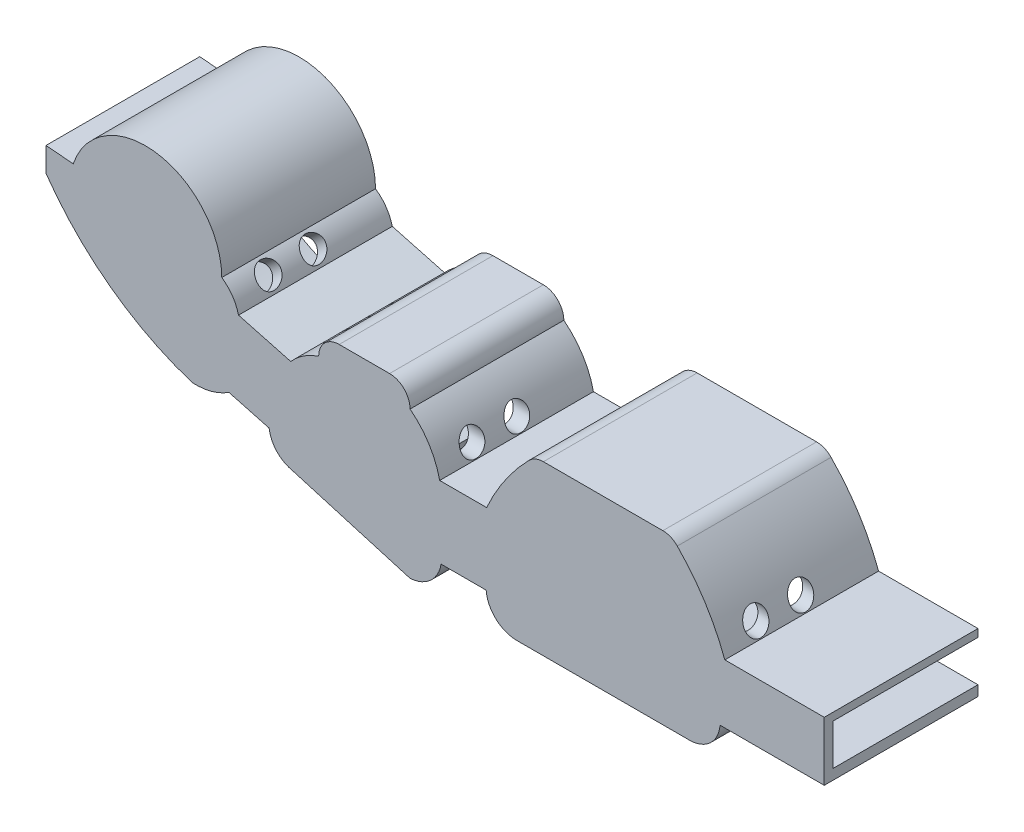
SolidWorks part; units mm, degrees
ref_plane "Front Plane" through (0, 0, 0) normal (0, 0, 1) x (1, 0, 0)
ref_plane "Top Plane" through (0, 0, 0) normal (0, 1, 0) x (1, 0, 0)
ref_plane "Right Plane" through (0, 0, 0) normal (1, 0, 0) x (0, 0, -1)
sketch "Sketch1" plane through (0, 0, 0) normal (0, 0, 1) x (1, 0, 0)
  line L23 (-11.1807, 10.652) -> (-11.4807, 9.152)
  line L24 (-11.4807, 9.152) -> (-11.7807, 10.652)
  line L25 (-11.7807, 10.652) -> (-12.4807, 10.652)
  line L36 (-12.4807, 10.652) -> (-12.7807, 9.152)
  line L40 (-12.7807, 9.152) -> (-13.0807, 10.652)
  line L41 (-13.0807, 10.652) -> (-13.7547, 10.652)
  line L47 (-13.7547, 10.652) -> (-14.0547, 9.152)
  line L48 (-14.0547, 9.152) -> (-14.3547, 10.652)
  line L49 (-14.3547, 10.652) -> (-15.0547, 10.652)
  line L50 (-15.0547, 10.652) -> (-15.3547, 9.152)
  line L51 (-15.3547, 9.152) -> (-15.6547, 10.652)
  line L52 (-15.6547, 10.652) -> (-16.3547, 10.652)
  line L53 (-16.3547, 10.652) -> (-16.6547, 9.152)
  line L54 (-16.6547, 9.152) -> (-16.9547, 10.652)
  line L55 (-16.9547, 10.652) -> (-17.6547, 10.652)
  line L80 (-17.6547, 10.652) -> (-17.9547, 9.152)
  line L167 (-44.1336, 10.6822) -> (-44.4336, 9.1822)
  line L170 (-46.0336, 10.6822) -> (-46.7336, 10.6822)
  line L171 (8.2817, 1.895) -> (-3.6348, 1.895)
  line L172 (-10.5067, 10.652) -> (-11.1807, 10.652)
  line L173 (-9.9067, 10.652) -> (-9.3532, 10.652)
  line L175 (-69.5436, 18.4578) -> (-69.8436, 19.5977)
  line L176 (-9.9067, 10.652) -> (-10.2067, 9.152)
  line L177 (-10.2067, 9.152) -> (-10.5067, 10.652)
  line L178 (-73.1421, 18.9938) -> (-73.4421, 17.6938)
  line L179 (-3.7183, -2.905) -> (8.2817, -2.905)
  line L180 (-2.7142, -4.105) -> (9.4817, -4.105)
  line L181 (-35.5381, 4.295) -> (-30.0408, 4.295)
  line L183 (9.4817, 2.795) -> (9.4817, -4.105)
  line L184 (8.2817, 1.895) -> (8.2817, -2.905)
  line L185 (-2.1578, 2.795) -> (9.4817, 2.795)
  line L186 (-77.5867, 9.2655) -> (-80.8842, 13.2092)
  line L187 (-45.4336, 10.6822) -> (-45.7336, 9.1822)
  line L188 (-66.9436, 17.8313) -> (-67.2436, 19.0854)
  line L189 (-57.9127, 0.2682) -> (-55.5052, -0.3779)
  line L190 (-81.6257, 12.3858) -> (-81.6257, 15.2174)
  line L192 (-42.8596, 10.6822) -> (-43.1596, 9.1822)
  line L193 (-43.1596, 9.1822) -> (-43.4596, 10.6822)
  line L194 (-44.7336, 10.6822) -> (-45.4336, 10.6822)
  line L195 (-80.8842, 13.2092) -> (-80.8842, 13.9453)
  line L196 (-44.4336, 9.1822) -> (-44.7336, 10.6822)
  line L197 (-64.3436, 15.6755) -> (-64.6436, 17.4876)
  line L198 (-70.5448, 19.5875) -> (-70.8448, 18.3969)
  line L199 (-60.3187, 8.3687) -> (-52.5921, 6.2951)
  line L200 (-23.1547, 9.152) -> (-23.4579, 10.6577)
  line L202 (-70.8448, 18.3969) -> (-71.1448, 19.5298)
  line L203 (-42.7174, 10.6822) -> (-42.8596, 10.6822)
  line L204 (-74.7402, 16.8139) -> (-75.0402, 17.886)
  line L205 (-78.8408, 12.3858) -> (-80.4985, 13.5047)
  line L206 (-73.4421, 17.6938) -> (-73.7421, 18.7169)
  line L207 (-47.0336, 9.1822) -> (-47.3336, 10.6822)
  line L208 (-64.0436, 16.8755) -> (-64.3436, 15.6755)
  line L209 (-80.8842, 13.9453) -> (-80.4985, 13.5047)
  line L210 (-65.6436, 16.9603) -> (-65.9436, 18.4574)
  line L211 (-67.9436, 19.313) -> (-68.2436, 18.263)
  line L212 (-37.0928, 3.095) -> (-29.0928, 3.095)
  line L213 (-62.7436, 14.8576) -> (-63.0436, 12.8576)
  line L214 (-68.2436, 18.263) -> (-68.5436, 19.4536)
  line L215 (-75.7418, 17.2662) -> (-76.0418, 15.3662)
  line L218 (-69.2436, 19.5578) -> (-69.5436, 18.4578)
  line L219 (-74.4402, 18.3139) -> (-74.7402, 16.8139)
  line L220 (-61.4607, 2.4628) -> (-53.62, 0.3587)
  line L222 (-63.0436, 12.8576) -> (-63.3436, 15.955)
  line L223 (-65.3436, 18.0603) -> (-65.6436, 16.9603)
  line L224 (-76.0418, 15.3662) -> (-76.3418, 16.5999)
  line L225 (-35.3722, -4.105) -> (-30.1012, -4.105)
  line L226 (-81.6257, 15.2174) -> (-78.4372, 14.9459)
  line L227 (-29.0971, -2.905) -> (-37.1235, -2.905)
  line L228 (-45.7336, 9.1822) -> (-46.0336, 10.6822)
  line L229 (-66.6436, 18.8313) -> (-66.9436, 17.8313)
  line L230 (-71.8426, 19.4048) -> (-72.1426, 18.1477)
  line L231 (-43.4596, 10.6822) -> (-44.1336, 10.6822)
  line L232 (-52.9727, 7.6397) -> (-59.0852, 9.2801)
  line L233 (-47.4174, 10.6822) -> (-47.3336, 10.6822)
  line L235 (-46.7336, 10.6822) -> (-47.0336, 9.1822)
  line L236 (-72.1426, 18.1477) -> (-72.4426, 19.2451)
  line L237 (-57.9127, 0.2682) -> (-60.21, 0.8847)
  line L238 (-19.2547, 9.152) -> (-19.5547, 10.652)
  line L239 (-17.9547, 9.152) -> (-18.2547, 10.652)
  line L240 (-20.2547, 10.652) -> (-20.5547, 9.152)
  line L241 (-18.2547, 10.652) -> (-18.9547, 10.652)
  line L242 (-18.9547, 10.652) -> (-19.2547, 9.152)
  line L243 (-20.8547, 10.652) -> (-21.5547, 10.652)
  line L244 (-20.5547, 9.152) -> (-20.8547, 10.652)
  line L245 (-19.5547, 10.652) -> (-20.2547, 10.652)
  line L246 (-21.5547, 10.652) -> (-21.8547, 9.152)
  line L247 (-22.1547, 10.652) -> (-22.8547, 10.652)
  line L248 (-22.8547, 10.652) -> (-23.1547, 9.152)
  line L249 (-21.8547, 9.152) -> (-22.1547, 10.652)
  line L253 (-23.3968, 12.2681) -> (-9.4143, 12.2681)
  line L254 (-26.0691, -6.2141) -> (-6.7463, -6.2141)
  line L255 (-6.3025, -7.4141) -> (-26.513, -7.4141)
  line L256 (-47.304, 12.2025) -> (-41.404, 12.2025)
  line L257 (-51.326, -2.5288) -> (-40.0703, -5.8983)
  line L258 (-39.0122, -7.3625) -> (-52.779, -3.3191)
  arc A66 (-2.7142, -4.105) -> (-6.3025, -7.4141) centre (-6.3025, -3.8141) cw
  arc A67 (-3.7183, -2.905) -> (-6.7463, -6.2141) centre (-6.7023, -3.2144) cw
  arc A69 (-7.343, 8.6822) -> (-9.3532, 10.652) centre (-10.3911, 7.5822) ccw
  arc A70 (-7.343, 8.6822) -> (-3.6348, 1.895) centre (-11.6135, 1.9424) cw
  arc A71 (-2.1578, 2.795) -> (-7.7202, 11.551) centre (-25.381, -5.8132) ccw
  arc A72 (-9.4143, 12.2681) -> (-7.7202, 11.551) centre (-9.4143, 9.9085) cw
  arc A73 (-62.0436, 11.2299) -> (-62.7436, 14.8576) centre (-70.0767, 11.5612) ccw
  arc A74 (-49.4174, 8.6822) -> (-52.5921, 6.2951) centre (-47.5158, 2.8486) ccw
  arc A75 (-23.3968, 12.2681) -> (-25.0909, 11.551) centre (-23.3968, 9.9085) ccw
  arc A76 (-75.0402, 17.886) -> (-75.7418, 17.2662) centre (-70.0767, 11.5612) ccw
  arc A77 (-29.0971, -2.905) -> (-26.0691, -6.2141) centre (-26.1131, -3.2144) ccw
  arc A78 (-81.6257, 12.3858) -> (-64.5211, -0.2669) centre (-54.2173, 31.5502) ccw
  arc A79 (-65.9436, 18.4574) -> (-66.6436, 18.8313) centre (-70.0767, 11.5612) ccw
  arc A80 (-69.8436, 19.5977) -> (-70.5448, 19.5875) centre (-70.0767, 11.5612) ccw
  arc A81 (-71.1448, 19.5298) -> (-71.8426, 19.4048) centre (-70.0767, 11.5612) ccw
  arc A82 (-47.304, 12.2025) -> (-49.704, 9.8025) centre (-47.304, 9.8025) ccw
  arc A83 (-40.0703, -5.8983) -> (-37.1235, -2.905) centre (-40.3823, -2.644) ccw
  arc A84 (-77.5867, 9.2655) -> (-64.963, 0.8179) centre (-56.8402, 26.6123) ccw
  arc A85 (-40.7174, 8.6822) -> (-42.7174, 10.6822) centre (-42.7174, 8.6822) ccw
  arc A86 (-47.4174, 10.6822) -> (-49.4174, 8.6822) centre (-47.4174, 8.6822) ccw
  arc A87 (-30.1012, -4.105) -> (-26.513, -7.4141) centre (-26.513, -3.8141) ccw
  arc A88 (-35.5381, 4.295) -> (-39.004, 9.8025) centre (-44.8924, 2.2526) ccw
  arc A89 (-67.2436, 19.0854) -> (-67.9436, 19.313) centre (-70.0767, 11.5612) ccw
  arc A90 (-72.4426, 19.2451) -> (-73.1421, 18.9938) centre (-70.0767, 11.5612) ccw
  arc A91 (-78.4372, 14.9459) -> (-61.0466, 12.1147) centre (-69.9779, 12.081) cw
  arc A92 (-63.3436, 15.955) -> (-64.0436, 16.8755) centre (-70.0767, 11.5612) ccw
  arc A93 (-64.963, 0.8179) -> (-61.4607, 2.4628) centre (-64.1865, 3.7157) ccw
  arc A94 (-73.7421, 18.7169) -> (-74.4402, 18.3139) centre (-70.0767, 11.5612) ccw
  arc A95 (-49.704, 9.8025) -> (-52.9727, 7.6397) centre (-47.422, 2.8022) ccw
  arc A96 (-24.9838, 9.9746) -> (-25.4681, 8.6822) centre (-23.5017, 8.6822) ccw
  arc A97 (-39.0122, -7.3625) -> (-35.3722, -4.105) centre (-39.2396, -3.446) ccw
  arc A98 (-76.3418, 16.5999) -> (-78.0314, 12.7286) centre (-70.0767, 11.5612) ccw
  arc A99 (-53.62, 0.3587) -> (-51.326, -2.5288) centre (-50.7468, 0.2864) ccw
  arc A100 (-60.3187, 8.3687) -> (-62.0436, 11.2299) centre (-64.3325, 7.8995) ccw
  arc A101 (-23.4579, 10.6577) -> (-24.9838, 9.9746) centre (-23.4814, 8.6645) ccw
  arc A102 (-68.5436, 19.4536) -> (-69.2436, 19.5578) centre (-70.0767, 11.5612) ccw
  arc A103 (-39.004, 9.8025) -> (-41.404, 12.2025) centre (-41.404, 9.8025) ccw
  arc A104 (-30.0408, 4.295) -> (-25.0909, 11.551) centre (-7.4301, -5.8132) cw
  arc A105 (-55.5052, -0.3779) -> (-52.779, -3.3191) centre (-52.084, 0.0591) ccw
  arc A106 (-64.6436, 17.4876) -> (-65.3436, 18.0603) centre (-70.0767, 11.5612) ccw
  arc A107 (-60.21, 0.8847) -> (-64.5211, -0.2669) centre (-64.1411, 6.9561) cw
  arc A108 (-37.0928, 3.095) -> (-40.7174, 8.6822) centre (-44.988, 1.9424) ccw
  arc A109 (-59.0852, 9.2801) -> (-61.0466, 12.1147) centre (-63.7933, 8.1183) ccw
  arc A110 (-25.4681, 8.6822) -> (-29.0928, 3.095) centre (-21.1976, 1.9424) ccw
  arc A111 (-78.0314, 12.7286) -> (-78.8408, 12.3858) centre (-71.5152, -3.7856) ccw
  dimension "D14" = 12
  dimension "D18" = 4.8
  dimension "D19" = 6.9
  dimension "D20" = 11.9164
extrude "Walls" add sketch "Sketch1" along normal blind 16 contours L242 region at (-36.8277, 4.9059, 0)
sketch "Sketch2" plane through (0, 0, 0) normal (0, 0, -1) x (-1, 0, 0)
  line L10 (59.0852, 9.2801) -> (52.9727, 7.6397)
  line L12 (59.0852, 9.2801) -> (52.9727, 7.6397)
  line L14 (47.304, 12.2025) -> (41.404, 12.2025)
  line L15 (2.1578, 2.795) -> (-9.4817, 2.795)
  line L16 (47.304, 12.2025) -> (41.404, 12.2025)
  line L17 (2.1578, 2.795) -> (-9.4817, 2.795)
  line L18 (-9.4817, 2.795) -> (-9.4817, -4.105)
  line L19 (35.5381, 4.295) -> (30.0408, 4.295)
  line L22 (35.5381, 4.295) -> (30.0408, 4.295)
  line L37 (-9.4817, 2.795) -> (-9.4817, -4.105)
  line L38 (-9.4817, -4.105) -> (2.7142, -4.105)
  line L39 (-9.4817, -4.105) -> (2.7142, -4.105)
  line L40 (23.3968, 12.2681) -> (9.4143, 12.2681)
  line L42 (23.3968, 12.2681) -> (9.4143, 12.2681)
  line L44 (6.3025, -7.4141) -> (26.513, -7.4141)
  line L47 (6.3025, -7.4141) -> (26.513, -7.4141)
  line L49 (30.1012, -4.105) -> (35.3722, -4.105)
  line L50 (30.1012, -4.105) -> (35.3722, -4.105)
  line L51 (39.0122, -7.3625) -> (52.779, -3.3191)
  line L52 (39.0122, -7.3625) -> (52.779, -3.3191)
  line L53 (55.5052, -0.3779) -> (60.21, 0.8847)
  line L54 (55.5052, -0.3779) -> (60.21, 0.8847)
  line L55 (81.6257, 12.3858) -> (81.6257, 15.2174)
  line L56 (81.6257, 12.3858) -> (81.6257, 15.2174)
  line L57 (81.6257, 15.2174) -> (78.4372, 14.9459)
  line L58 (81.6257, 15.2174) -> (78.4372, 14.9459)
  arc A16 (9.4143, 12.2681) -> (7.7202, 11.551) centre (9.4143, 9.9085) ccw
  arc A17 (9.4143, 12.2681) -> (7.7202, 11.551) centre (9.4143, 9.9085) ccw
  arc A18 (52.9727, 7.6397) -> (49.704, 9.8025) centre (47.422, 2.8022) ccw
  arc A19 (52.9727, 7.6397) -> (49.704, 9.8025) centre (47.422, 2.8022) ccw
  arc A20 (49.704, 9.8025) -> (47.304, 12.2025) centre (47.304, 9.8025) ccw
  arc A21 (49.704, 9.8025) -> (47.304, 12.2025) centre (47.304, 9.8025) ccw
  arc A22 (41.404, 12.2025) -> (39.004, 9.8025) centre (41.404, 9.8025) ccw
  arc A23 (41.404, 12.2025) -> (39.004, 9.8025) centre (41.404, 9.8025) ccw
  arc A24 (39.004, 9.8025) -> (35.5381, 4.295) centre (44.8924, 2.2526) ccw
  arc A25 (7.7202, 11.551) -> (2.1578, 2.795) centre (25.381, -5.8132) ccw
  arc A26 (7.7202, 11.551) -> (2.1578, 2.795) centre (25.381, -5.8132) ccw
  arc A27 (2.7142, -4.105) -> (6.3025, -7.4141) centre (6.3025, -3.8141) ccw
  arc A28 (2.7142, -4.105) -> (6.3025, -7.4141) centre (6.3025, -3.8141) ccw
  arc A29 (39.004, 9.8025) -> (35.5381, 4.295) centre (44.8924, 2.2526) ccw
  arc A30 (30.0408, 4.295) -> (25.0909, 11.551) centre (7.4301, -5.8132) ccw
  arc A31 (30.0408, 4.295) -> (25.0909, 11.551) centre (7.4301, -5.8132) ccw
  arc A32 (25.0909, 11.551) -> (23.3968, 12.2681) centre (23.3968, 9.9085) ccw
  arc A33 (25.0909, 11.551) -> (23.3968, 12.2681) centre (23.3968, 9.9085) ccw
  arc A34 (26.513, -7.4141) -> (30.1012, -4.105) centre (26.513, -3.8141) ccw
  arc A35 (26.513, -7.4141) -> (30.1012, -4.105) centre (26.513, -3.8141) ccw
  arc A54 (35.3722, -4.105) -> (39.0122, -7.3625) centre (39.2396, -3.446) ccw
  arc A55 (35.3722, -4.105) -> (39.0122, -7.3625) centre (39.2396, -3.446) ccw
  arc A56 (52.779, -3.3191) -> (55.5052, -0.3779) centre (52.084, 0.0591) ccw
  arc A57 (52.779, -3.3191) -> (55.5052, -0.3779) centre (52.084, 0.0591) ccw
  arc A58 (60.21, 0.8847) -> (64.5211, -0.2669) centre (64.1411, 6.9561) ccw
  arc A59 (60.21, 0.8847) -> (64.5211, -0.2669) centre (64.1411, 6.9561) ccw
  arc A60 (64.5211, -0.2669) -> (81.6257, 12.3858) centre (54.2173, 31.5502) ccw
  arc A61 (64.5211, -0.2669) -> (81.6257, 12.3858) centre (54.2173, 31.5502) ccw
  arc A62 (78.4372, 14.9459) -> (61.0466, 12.1147) centre (69.9779, 12.081) ccw
  arc A63 (78.4372, 14.9459) -> (61.0466, 12.1147) centre (69.9779, 12.081) ccw
  arc A64 (61.0466, 12.1147) -> (59.0852, 9.2801) centre (63.7933, 8.1183) ccw
  arc A65 (61.0466, 12.1147) -> (59.0852, 9.2801) centre (63.7933, 8.1183) ccw
  dimension "D1" = 0
extrude "Base" add sketch "Sketch2" along normal blind 1
sketch "Sketch3" [suppressed] plane through (0, 0, 0) normal (0, 0, 1) x (1, 0, 0)
  line L4 (-65.1711, 5.3832) -> (-63.3958, 4.9067) construction
  line L5 (-84.8697, 19.5134) -> (-85.1843, 17.3997) construction
  line L6 (-51.77, 3.095) -> (-68.5693, 3.095) construction
  line L7 (-68.5693, 6.2951) -> (-68.5693, 3.095) construction
  line L8 (-51.77, 3.095) -> (-54.6697, 3.095) construction
  line L9 (-68.5693, 6.2951) -> (-65.1711, 5.3832) construction
  line L10 (-56.4697, 3.095) -> (-54.6697, 3.095) construction
  line L11 (-80.595, 9.5224) -> (-82.2789, 9.9743)
  line L12 (-80.595, 9.5224) -> (-76.2959, 8.3687) construction
  line L13 (-91.8537, 12.2226) -> (-90.116, 11.8146)
  line L14 (-82.2789, 9.9743) -> (-90.116, 11.8146) construction
  line L15 (-40.77, 3.095) -> (-37.27, 3.095) construction
  line L16 (-3.6422, 1.595) -> (-7.1422, 1.595) construction
  line L17 (-40.77, 3.095) -> (-3.7183, 3.095) construction
  line L18 (-22.2442, 8.652) -> (-22.2442, 3.095) construction
  line L19 (-22.8547, 10.652) -> (-22.1547, 10.652) construction
  line L20 (-22.2442, 10.652) -> (-22.2442, 8.652) construction
  line L21 (-37.27, 3.095) -> (-34.1769, 3.095) construction
  line L22 (-11.7175, 3.095) -> (-7.1422, 1.595) construction
  arc A1 (-82.2789, 9.9743) -> (-90.116, 11.8146) centre (-86.0365, 11.58) ccw
  arc A2 (-91.8537, 12.2226) -> (-80.595, 9.5224) centre (-86.0443, 11.6231) cw
  arc A3 (-54.6697, 3.095) -> (-65.1711, 5.3832) centre (-60.1697, 3.095) ccw construction
  arc A4 (-84.5208, 19.4536) -> (-85.2208, 19.5578) centre (-86.0539, 11.5612) ccw construction
  arc A5 (-56.4697, 3.095) -> (-63.3958, 4.9067) centre (-60.1697, 3.095) ccw construction
  arc A6 (-3.6422, 1.595) -> (-7.343, 8.6822) centre (-11.6135, 1.9424) ccw construction
  arc A7 (-7.1422, 1.595) -> (-37.27, 3.095) centre (-22.9472, -12.5401) ccw construction
  arc A8 (-11.7175, 3.095) -> (-34.1769, 3.095) centre (-22.9472, -12.5401) ccw construction
  dimension "D1" = 11
  dimension "D2" = 2.137
  dimension "D3" = 7.4
  dimension "D8" = 38.5
  dimension "D4" = 3.5184
  dimension "D5" = 3.5
  dimension "D6" = 3.5
  dimension "D7" = 2
sketch "Sketch4" [suppressed] plane through (0, 0, 16) normal (0, 0, 1) x (1, 0, 0)
  line L7 (-69.5947, 0.3005) -> (-71.4824, -0.3779)
  line L10 (-71.4824, -0.3779) -> (-76.1872, 0.8847)
  line L11 (-76.1872, 0.8847) -> (-77.6773, 2.0433)
  line L12 (-40.77, 3.095) -> (-41.1043, 4.1128)
  line L13 (-41.1043, 4.1128) -> (-49.5364, 4.1128)
  line L16 (-67.7226, 6.3478) -> (-68.9499, 7.6397)
  line L17 (-68.9499, 7.6397) -> (-75.0624, 9.2801)
  line L18 (-75.0624, 9.2801) -> (-76.3177, 7.7352)
  line L19 (-49.5364, 4.1128) -> (-51.77, 3.095)
  line L20 (-40.7743, -2.905) -> (-41.0926, -4.1129)
  line L21 (-41.0926, -4.1129) -> (-49.3636, -4.1129)
  line L22 (-49.3636, -4.1129) -> (-51.8007, -2.905)
  arc A0 (-67.7226, 6.3478) -> (-76.3177, 7.7352) centre (-69.7742, 20.955) cw
  arc A1 (-69.5947, 0.3005) -> (-77.6773, 2.0433) centre (-76.3689, -11.5028) ccw
  arc A2 (-40.7743, -2.905) -> (-51.8007, -2.905) centre (-46.2875, -28.5004) ccw
  arc A3 (-40.77, 3.095) -> (-51.77, 3.095) centre (-46.27, 28.5687) cw
extrude "Joint Width" [suppressed] add sketch "Sketch4" against normal blind 16
ref_plane "SideAnchorPlane" through (0, 0, 2.5) normal (0, 0, 1) x (1, 0, 0)
ref_plane "CentralAnchorPlane" through (0, 0, 13) normal (0, 0, 1) x (1, 0, 0)
sketch "Sketch5" [suppressed] plane through (0, 0, 3) normal (0, 0, 1) x (1, 0, 0)
  line L0 (-76.2959, 8.3687) -> (-68.5693, 6.2951) construction
  line L1 (-76.592, 9.4835) -> (-67.8744, 7.144) construction
  line L2 (-77.4258, 10.7304) -> (-66.9487, 7.9187) construction
  line L3 (-76.592, 9.4835) -> (-88.7757, 4.7797)
  line L4 (-77.4258, 10.7304) -> (-90.1205, 5.8293)
  line L5 (-78.0158, 11.7317) -> (-91.096, 6.6818)
  line L6 (-76.2959, 8.3687) -> (-87.6359, 3.9906)
  line L7 (-78.0158, 11.7317) -> (-77.4258, 10.7304)
  line L9 (-76.592, 9.4835) -> (-76.0479, 8.9395)
  line L10 (-76.0479, 8.9395) -> (-76.2959, 8.3687)
  line L11 (-91.096, 6.6818) -> (-91.096, 6.0024)
  line L12 (-91.096, 6.0024) -> (-90.1205, 5.8293)
  line L13 (-88.7757, 4.7797) -> (-88.5883, 3.9906)
  line L14 (-88.5883, 3.9906) -> (-87.6359, 3.9906)
  arc A0 (-76.2959, 8.3687) -> (-78.0208, 11.2299) centre (-80.3097, 7.8995) ccw construction
  arc A1 (-65.3947, 8.6822) -> (-68.5693, 6.2951) centre (-63.493, 2.8486) ccw construction
  arc A2 (-76.2959, 8.3687) -> (-78.0208, 11.2299) centre (-80.3097, 7.8995) ccw construction
  arc A4 (-93.5639, 9.2655) -> (-80.9402, 0.8179) centre (-72.8174, 26.6123) ccw construction
  arc A5 (-93.5639, 9.2655) -> (-80.9402, 0.8179) centre (-72.8174, 26.6123) ccw construction
  dimension "D1" = 1
  dimension "D2" = 1.5
  dimension "D3" = 1.1466
  dimension "D4" = 1.1466
extrude "Boss-Extrude2" [suppressed] add sketch "Sketch5" along normal blind 1 and the other way blind 1 separate body
sketch "Sketch6" [suppressed] plane through (0, 0, 4) normal (0, 0, 1) x (1, 0, 0)
  line L1 (-87.6359, 3.9906) -> (-76.2959, 8.3687)
  line L4 (-78.0158, 11.7317) -> (-91.096, 6.6818)
  line L5 (-91.096, 6.6818) -> (-91.7792, 6.284)
  line L6 (-91.7792, 6.284) -> (-88.4163, 3.7031)
  line L7 (-88.4163, 3.7031) -> (-87.6359, 3.9906)
  line L8 (-78.0158, 11.7317) -> (-75.9969, 10.8669)
  line L9 (-75.9969, 10.8669) -> (-76.2959, 8.3687)
  arc A0 (-93.5639, 9.2655) -> (-80.9402, 0.8179) centre (-72.8174, 26.6123) ccw construction
extrude "Boss-Extrude4" [suppressed] add sketch "Sketch6" along normal blind 1
sketch "Sketch7" [suppressed] plane through (0, 0, 2) normal (0, 0, -1) x (-1, 0, 0)
  line L0 (87.6359, 3.9906) -> (90.1015, 4.9746)
  line L1 (90.1015, 4.9746) -> (91.096, 6.6818)
  line L2 (91.096, 6.6818) -> (78.0158, 11.7317)
  line L3 (78.0158, 11.7317) -> (76.2959, 10.4542)
  line L4 (76.2959, 10.4542) -> (76.2959, 8.3687)
  line L5 (76.2959, 8.3687) -> (87.6359, 3.9906)
extrude "Boss-Extrude5" [suppressed] add sketch "Sketch7" along normal blind 1
extrude "Boss-Extrude6" [suppressed] add sketch "Sketch3" along normal up to surface (16 mm away)
ref_plane "Plane3" through (-55, 0, 0) normal (1, 0, 0) x (0, 0, -1)
sketch "Sketch14" plane through (-55, 0, 0) normal (1, 0, 0) x (0, 0, -1)
  line L0 (-16, 3.095) -> (1, 3.095) construction
  line L1 (1, 2.795) -> (1, 11.551) construction
  line L2 (-16, 8.4472) -> (1, 8.4472) construction
  line L3 (-16, 11.551) -> (-16, 2.795) construction
  line L4 (-7.5, 8.4472) -> (-7.5, 3.095) construction
  line L6 (-7.5, 5.7711) -> (-16, 5.7711) construction
  line L7 (-16, 2.795) -> (-16, 3.095) construction
  line L8 (-16, 8.4472) -> (-16, 3.095) construction
  circle A4 centre (-12.75, 5.7711) radius 1.4
  circle A5 centre (-2.25, 5.7711) radius 1.4 construction
  circle A6 centre (-7.5, 5.7711) radius 1.4
  dimension "D1" = 2.8
  dimension "D2" = 5.25
  dimension "D3" = 0.3
extrude "Cut-Extrude2" cut sketch "Sketch14" along normal up to surface (26.8022 mm away) up to face at (-27.5858, 6.0868, 8)
sketch "Sketch15" plane through (0, 0, 0) normal (1, 0, 0) x (0, 0, -1)
  line L1 (-16, 2.795) -> (1, 2.795) construction
  line L5 (1, 2.795) -> (1, 5.795) construction
  line L6 (1, 2.795) -> (1, 11.551) construction
  line L7 (1, 5.795) -> (-16, 5.795) construction
  line L8 (-7.5, 5.795) -> (-7.5, 2.795) construction
  line L9 (-16, 11.551) -> (-16, 2.795) construction
  line L10 (-7.5, 4.295) -> (-16, 4.295) construction
  circle A4 centre (-12.75, 4.295) radius 1.4
  circle A5 centre (-2.25, 4.295) radius 1.4 construction
  circle A6 centre (-7.5, 4.295) radius 1.4
  dimension "D2" = 5.25
  dimension "D1" = 2.8
extrude "Cut-Extrude3" cut sketch "Sketch15" against normal up to surface (3.9894 mm away) up to face at (-5.0502, 5.5283, 8)
ref_plane "Plane4" through (-30.1263, -25.259, 0) normal (0.7663, 0.6425, 0) x (0, 0, -1)
sketch "Sketch16" plane through (-30.1263, -25.259, 0) normal (0.7663, 0.6425, 0) x (0, 0, -1)
  line L1 (-2.2201, 49.6951) -> (-13, 49.6951) construction
  line L2 (-13, 55) -> (-13, -55) construction
  line L3 (-16, 48.5053) -> (-16, 45.0729) construction
  line L6 (-16, 46.7891) -> (1, 46.7891) construction
  line L7 (-7.61, 49.6951) -> (-13, 49.6951) construction
  line L12 (-16, 48.5053) -> (1, 48.5053) construction
  line L13 (-7.5, 48.5053) -> (-7.5, 45.0729) construction
  circle A0 centre (-2.2201, 49.6951) radius 1.4 construction
  circle A1 centre (-12.86, 49.6951) radius 1.4 construction
  circle A2 centre (-12.75, 46.7891) radius 1.4
  circle A3 centre (-2.25, 46.7891) radius 1.4 construction
  circle A4 centre (-7.5, 46.7891) radius 1.4
  dimension "D1" = 2.8
  dimension "D4" = 5.25
  dimension "D5" = 2.8
  dimension "D3" = 5.25
extrude "Cut-Extrude4" cut sketch "Sketch16" against normal up to surface and the other way up to surface up to face at (-73.5899, 5.3613, 7.5) other way up to face at (-59.9357, 10.7875, 7.5)
ref_plane "Plane5" through (-49.2204, 17.9364, 0) normal (-0.9396, 0.3424, 0) x (0, 0, -1)
sketch "Sketch18" plane through (-49.2204, 17.9364, 0) normal (-0.9396, 0.3424, 0) x (0, 0, -1)
  line L0 (-16, 8.7623) -> (0, 8.7623) construction
  line L1 (-16, 7.8123) -> (-16, 9.3835) construction
  line L2 (-16, 10.9591) -> (-16, 7.8079) construction
  line L3 (-16, 9.3835) -> (1, 9.3835) construction
  line L4 (1, 7.8079) -> (1, 10.9591) construction
  line L5 (-16, 7.8123) -> (1, 7.8123) construction
  line L6 (-7.5, 9.3835) -> (-7.5, 7.8123) construction
  line L14 (-7.5, 9.3835) -> (-16, 9.3835) construction
  circle A2 centre (-12.75, 9.3835) radius 1.4
  circle A3 centre (-2.25, 9.3835) radius 1.4 construction
  circle A4 centre (-7.5, 9.3835) radius 1.4
  dimension "D1" = 2.8
  dimension "D3" = 17
  dimension "D4" = 0.95
extrude "Cut-Extrude5" cut sketch "Sketch18" against normal up to surface (1.3124 mm away) up to face at (-51.6727, 7.1718, 9.1219)
sketch "Sketch19" plane through (0, 0, 0) normal (0, 0, 1) x (1, 0, 0)
  line L477 (-11.1807, 10.652) -> (-11.4807, 9.152)
  line L490 (-11.4807, 9.152) -> (-11.7807, 10.652)
  line L542 (-11.7807, 10.652) -> (-12.4807, 10.652)
  line L685 (-12.4807, 10.652) -> (-12.7807, 9.152)
  line L686 (-12.7807, 9.152) -> (-13.0807, 10.652)
  line L687 (-13.0807, 10.652) -> (-13.7547, 10.652)
  line L688 (-13.7547, 10.652) -> (-14.0547, 9.152)
  line L689 (-14.0547, 9.152) -> (-14.3547, 10.652)
  line L690 (-14.3547, 10.652) -> (-15.0547, 10.652)
  line L691 (-15.0547, 10.652) -> (-15.3547, 9.152)
  line L692 (-15.3547, 9.152) -> (-15.6547, 10.652)
  line L693 (-15.6547, 10.652) -> (-16.3547, 10.652)
  line L694 (-16.3547, 10.652) -> (-16.6547, 9.152)
  line L695 (-16.6547, 9.152) -> (-16.9547, 10.652)
  line L696 (-16.9547, 10.652) -> (-17.6547, 10.652)
  line L697 (-17.6547, 10.652) -> (-17.9547, 9.152)
  line L698 (-44.1336, 10.6822) -> (-44.4336, 9.1822)
  line L699 (-46.0336, 10.6822) -> (-46.7336, 10.6822)
  line L700 (8.2817, 1.895) -> (-3.6348, 1.895)
  line L701 (-10.5067, 10.652) -> (-11.1807, 10.652)
  line L702 (-9.9067, 10.652) -> (-9.3532, 10.652)
  line L703 (-69.5436, 18.4578) -> (-69.8436, 19.5977)
  line L704 (-9.9067, 10.652) -> (-10.2067, 9.152)
  line L705 (-10.2067, 9.152) -> (-10.5067, 10.652)
  line L706 (-73.1421, 18.9938) -> (-73.4421, 17.6938)
  line L707 (-3.7183, -2.905) -> (8.2817, -2.905)
  line L711 (8.2817, 1.895) -> (8.2817, -2.905)
  line L713 (-77.5867, 9.2655) -> (-80.8842, 13.2092)
  line L714 (-45.4336, 10.6822) -> (-45.7336, 9.1822)
  line L715 (-66.9436, 17.8313) -> (-67.2436, 19.0854)
  line L718 (-42.8596, 10.6822) -> (-43.1596, 9.1822)
  line L719 (-43.1596, 9.1822) -> (-43.4596, 10.6822)
  line L720 (-44.7336, 10.6822) -> (-45.4336, 10.6822)
  line L721 (-80.8842, 13.2092) -> (-80.8842, 13.9453)
  line L722 (-44.4336, 9.1822) -> (-44.7336, 10.6822)
  line L723 (-64.3436, 15.6755) -> (-64.6436, 17.4876)
  line L724 (-70.5448, 19.5875) -> (-70.8448, 18.3969)
  line L725 (-60.3187, 8.3687) -> (-52.5921, 6.2951)
  line L726 (-23.1547, 9.152) -> (-23.4579, 10.6577)
  line L727 (-70.8448, 18.3969) -> (-71.1448, 19.5298)
  line L728 (-42.7174, 10.6822) -> (-42.8596, 10.6822)
  line L729 (-74.7402, 16.8139) -> (-75.0402, 17.886)
  line L730 (-78.8408, 12.3858) -> (-80.4985, 13.5047)
  line L731 (-73.4421, 17.6938) -> (-73.7421, 18.7169)
  line L732 (-47.0336, 9.1822) -> (-47.3336, 10.6822)
  line L733 (-64.0436, 16.8755) -> (-64.3436, 15.6755)
  line L734 (-80.8842, 13.9453) -> (-80.4985, 13.5047)
  line L735 (-65.6436, 16.9603) -> (-65.9436, 18.4574)
  line L736 (-67.9436, 19.313) -> (-68.2436, 18.263)
  line L737 (-37.0928, 3.095) -> (-29.0928, 3.095)
  line L738 (-62.7436, 14.8576) -> (-63.0436, 12.8576)
  line L739 (-68.2436, 18.263) -> (-68.5436, 19.4536)
  line L740 (-75.7418, 17.2662) -> (-76.0418, 15.3662)
  line L741 (-69.2436, 19.5578) -> (-69.5436, 18.4578)
  line L742 (-74.4402, 18.3139) -> (-74.7402, 16.8139)
  line L743 (-61.4607, 2.4628) -> (-53.62, 0.3587)
  line L744 (-63.0436, 12.8576) -> (-63.3436, 15.955)
  line L745 (-65.3436, 18.0603) -> (-65.6436, 16.9603)
  line L746 (-76.0418, 15.3662) -> (-76.3418, 16.5999)
  line L749 (-29.0971, -2.905) -> (-37.1235, -2.905)
  line L750 (-45.7336, 9.1822) -> (-46.0336, 10.6822)
  line L751 (-66.6436, 18.8313) -> (-66.9436, 17.8313)
  line L752 (-71.8426, 19.4048) -> (-72.1426, 18.1477)
  line L753 (-43.4596, 10.6822) -> (-44.1336, 10.6822)
  line L755 (-47.4174, 10.6822) -> (-47.3336, 10.6822)
  line L756 (-46.7336, 10.6822) -> (-47.0336, 9.1822)
  line L757 (-72.1426, 18.1477) -> (-72.4426, 19.2451)
  line L759 (-19.2547, 9.152) -> (-19.5547, 10.652)
  line L760 (-17.9547, 9.152) -> (-18.2547, 10.652)
  line L761 (-20.2547, 10.652) -> (-20.5547, 9.152)
  line L762 (-18.2547, 10.652) -> (-18.9547, 10.652)
  line L763 (-18.9547, 10.652) -> (-19.2547, 9.152)
  line L764 (-20.8547, 10.652) -> (-21.5547, 10.652)
  line L765 (-20.5547, 9.152) -> (-20.8547, 10.652)
  line L766 (-19.5547, 10.652) -> (-20.2547, 10.652)
  line L767 (-21.5547, 10.652) -> (-21.8547, 9.152)
  line L768 (-22.1547, 10.652) -> (-22.8547, 10.652)
  line L769 (-22.8547, 10.652) -> (-23.1547, 9.152)
  line L770 (-21.8547, 9.152) -> (-22.1547, 10.652)
  line L772 (-26.0691, -6.2141) -> (-6.7463, -6.2141)
  line L775 (-51.326, -2.5288) -> (-40.0703, -5.8983)
  arc A251 (-3.7183, -2.905) -> (-6.7463, -6.2141) centre (-6.7023, -3.2144) cw
  arc A252 (-7.343, 8.6822) -> (-9.3532, 10.652) centre (-10.3911, 7.5822) ccw
  arc A253 (-7.343, 8.6822) -> (-3.6348, 1.895) centre (-11.6135, 1.9424) cw
  arc A256 (-62.0436, 11.2299) -> (-62.7436, 14.8576) centre (-70.0767, 11.5612) ccw
  arc A257 (-49.4174, 8.6822) -> (-52.5921, 6.2951) centre (-47.5158, 2.8486) ccw
  arc A259 (-75.0402, 17.886) -> (-75.7418, 17.2662) centre (-70.0767, 11.5612) ccw
  arc A260 (-29.0971, -2.905) -> (-26.0691, -6.2141) centre (-26.1131, -3.2144) ccw
  arc A262 (-65.9436, 18.4574) -> (-66.6436, 18.8313) centre (-70.0767, 11.5612) ccw
  arc A263 (-69.8436, 19.5977) -> (-70.5448, 19.5875) centre (-70.0767, 11.5612) ccw
  arc A264 (-71.1448, 19.5298) -> (-71.8426, 19.4048) centre (-70.0767, 11.5612) ccw
  arc A266 (-40.0703, -5.8983) -> (-37.1235, -2.905) centre (-40.3823, -2.644) ccw
  arc A267 (-77.5867, 9.2655) -> (-64.963, 0.8179) centre (-56.8402, 26.6123) ccw
  arc A268 (-40.7174, 8.6822) -> (-42.7174, 10.6822) centre (-42.7174, 8.6822) ccw
  arc A269 (-47.4174, 10.6822) -> (-49.4174, 8.6822) centre (-47.4174, 8.6822) ccw
  arc A272 (-67.2436, 19.0854) -> (-67.9436, 19.313) centre (-70.0767, 11.5612) ccw
  arc A273 (-72.4426, 19.2451) -> (-73.1421, 18.9938) centre (-70.0767, 11.5612) ccw
  arc A275 (-63.3436, 15.955) -> (-64.0436, 16.8755) centre (-70.0767, 11.5612) ccw
  arc A276 (-64.963, 0.8179) -> (-61.4607, 2.4628) centre (-64.1865, 3.7157) ccw
  arc A277 (-73.7421, 18.7169) -> (-74.4402, 18.3139) centre (-70.0767, 11.5612) ccw
  arc A279 (-24.9838, 9.9746) -> (-25.4681, 8.6822) centre (-23.5017, 8.6822) ccw
  arc A281 (-76.3418, 16.5999) -> (-78.0314, 12.7286) centre (-70.0767, 11.5612) ccw
  arc A282 (-53.62, 0.3587) -> (-51.326, -2.5288) centre (-50.7468, 0.2864) ccw
  arc A283 (-60.3187, 8.3687) -> (-62.0436, 11.2299) centre (-64.3325, 7.8995) ccw
  arc A284 (-23.4579, 10.6577) -> (-24.9838, 9.9746) centre (-23.4814, 8.6645) ccw
  arc A285 (-68.5436, 19.4536) -> (-69.2436, 19.5578) centre (-70.0767, 11.5612) ccw
  arc A289 (-64.6436, 17.4876) -> (-65.3436, 18.0603) centre (-70.0767, 11.5612) ccw
  arc A291 (-37.0928, 3.095) -> (-40.7174, 8.6822) centre (-44.988, 1.9424) ccw
  arc A293 (-25.4681, 8.6822) -> (-29.0928, 3.095) centre (-21.1976, 1.9424) ccw
  arc A294 (-78.0314, 12.7286) -> (-78.8408, 12.3858) centre (-71.5152, -3.7856) ccw
  dimension "D1" = 4.8
  dimension "D4" = 12
  dimension "D5" = 11.9164
extrude "Cut-Extrude6" cut sketch "Sketch19" against normal up to surface (1 mm away) up to face at (-37.1912, 4.8771, -1)
sketch "Sketch20" plane through (0, 0, 0) normal (0, 0, 1) x (1, 0, 0)
  line L0 (-78.6793, 6.0116) -> (-76.2003, 8.4287)
  line L1 (-75.866, 8.0563) -> (-78.3302, 5.6536)
  line L2 (-76.2003, 8.4287) -> (-75.866, 8.0563)
  line L3 (-78.3302, 5.6536) -> (-78.6793, 6.0116)
  line L4 (-47.0226, -6.2559) -> (-45.9351, -2.2035)
  line L5 (-66.9588, 2.1835) -> (-67.9904, -0.5519)
  line L6 (-45.4522, -2.3331) -> (-46.5397, -6.3855)
  line L7 (-46.5397, -6.3855) -> (-47.0226, -6.2559)
  line L8 (-45.4522, -2.3331) -> (-45.9351, -2.2035)
  line L9 (-67.9904, -0.5519) -> (-67.5225, -0.7283)
  line L10 (-16.6675, -3.3719) -> (-16.1675, -3.3719)
  line L11 (-16.6675, -3.3719) -> (-16.6675, -9.3408)
  line L12 (-16.6675, -9.3408) -> (-16.1675, -9.3408)
  line L13 (-16.1675, -3.3719) -> (-16.1675, -9.3408)
  line L14 (-67.5225, -0.7283) -> (-66.4909, 2.0071)
  line L15 (-66.4909, 2.0071) -> (-66.9588, 2.1835)
  line L16 (-40.201, -5.9144) -> (-52.7567, -2.5449) construction
  line L17 (-80.8842, 13.2092) -> (-64.963, 0.8179) construction
  dimension "D1" = 0.5
  dimension "D2" = 0.5
  dimension "D3" = 0.5
  dimension "D4" = 0.5
extrude "Cut-Extrude7" cut sketch "Sketch20" along normal blind 13 from offset 1
sketch "Sketch21" plane through (0, 0, 0) normal (0, 0, 1) x (1, 0, 0)
  line L0 (9.4817, 2.795) -> (9.4817, -4.105) construction
  line L3 (8.2817, -2.905) -> (9.4817, -2.905)
  line L4 (9.4817, 1.895) -> (9.4817, -2.905)
  line L5 (8.2817, -2.905) -> (8.2817, 1.895)
  line L6 (8.2817, 1.895) -> (9.4817, 1.895)
  dimension "D1" = 4.8
extrude "Cut-Extrude8" cut sketch "Sketch21" against normal up to surface and the other way up to surface up to face at (-42.8342, 10.9539, -1) other way up to face at (-42.8342, 10.9539, 16)
ref_plane "Plane6" through (0, 0, 16) normal (0, 0, 1) x (1, 0, 0)
sketch "Sketch22" plane through (0, 0, 16) normal (0, 0, 1) x (1, 0, 0)
  line L288 (-2.7142, -4.105) -> (9.4817, -4.105)
  line L289 (-35.5381, 4.295) -> (-30.0408, 4.295)
  line L290 (9.4817, 2.795) -> (9.4817, -4.105)
  line L292 (-2.1578, 2.795) -> (9.4817, 2.795)
  line L296 (-57.9127, 0.2682) -> (-55.5052, -0.3779)
  line L297 (-81.6257, 12.3858) -> (-81.6257, 15.2174)
  line L327 (-35.3722, -4.105) -> (-30.1012, -4.105)
  line L328 (-81.6257, 15.2174) -> (-78.4372, 14.9459)
  line L334 (-52.9727, 7.6397) -> (-59.0852, 9.2801)
  line L338 (-57.9127, 0.2682) -> (-60.21, 0.8847)
  line L351 (-23.3968, 12.2681) -> (-9.4143, 12.2681)
  line L353 (-6.3025, -7.4141) -> (-26.513, -7.4141)
  line L354 (-47.304, 12.2025) -> (-41.404, 12.2025)
  line L356 (-39.0122, -7.3625) -> (-52.779, -3.3191)
  arc A120 (-2.7142, -4.105) -> (-6.3025, -7.4141) centre (-6.3025, -3.8141) cw
  arc A124 (-2.1578, 2.795) -> (-7.7202, 11.551) centre (-25.381, -5.8132) ccw
  arc A125 (-9.4143, 12.2681) -> (-7.7202, 11.551) centre (-9.4143, 9.9085) cw
  arc A128 (-23.3968, 12.2681) -> (-25.0909, 11.551) centre (-23.3968, 9.9085) ccw
  arc A131 (-81.6257, 12.3858) -> (-64.5211, -0.2669) centre (-54.2173, 31.5502) ccw
  arc A135 (-47.304, 12.2025) -> (-49.704, 9.8025) centre (-47.304, 9.8025) ccw
  arc A140 (-30.1012, -4.105) -> (-26.513, -7.4141) centre (-26.513, -3.8141) ccw
  arc A141 (-35.5381, 4.295) -> (-39.004, 9.8025) centre (-44.8924, 2.2526) ccw
  arc A144 (-78.4372, 14.9459) -> (-61.0466, 12.1147) centre (-69.9779, 12.081) cw
  arc A148 (-49.704, 9.8025) -> (-52.9727, 7.6397) centre (-47.422, 2.8022) ccw
  arc A150 (-39.0122, -7.3625) -> (-35.3722, -4.105) centre (-39.2396, -3.446) ccw
  arc A156 (-39.004, 9.8025) -> (-41.404, 12.2025) centre (-41.404, 9.8025) ccw
  arc A157 (-30.0408, 4.295) -> (-25.0909, 11.551) centre (-7.4301, -5.8132) cw
  arc A158 (-55.5052, -0.3779) -> (-52.779, -3.3191) centre (-52.084, 0.0591) ccw
  arc A160 (-60.21, 0.8847) -> (-64.5211, -0.2669) centre (-64.1411, 6.9561) cw
  arc A162 (-59.0852, 9.2801) -> (-61.0466, 12.1147) centre (-63.7933, 8.1183) ccw
  dimension "D2" = 6.9
extrude "Boss-Extrude7" add sketch "Sketch22" along normal blind 1
